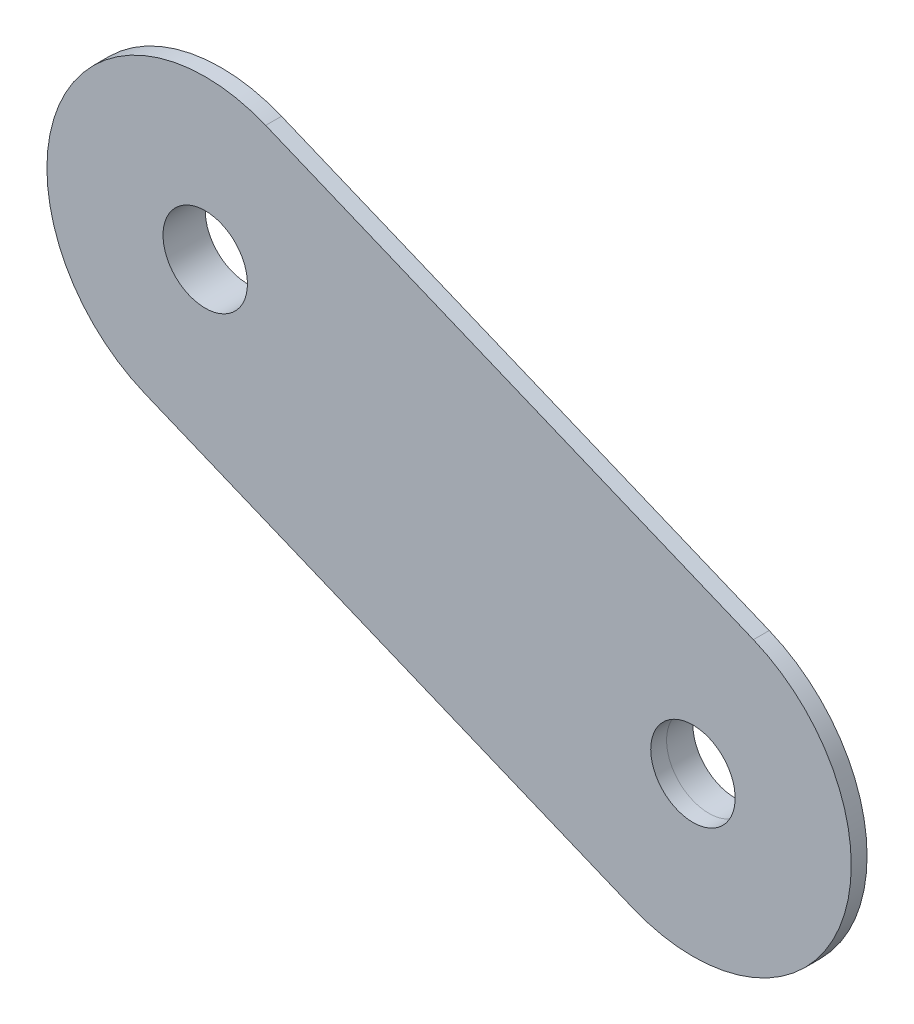
SolidWorks part; units mm, degrees
ref_plane "Front Plane" through (0, 0, 0) normal (0, 0, 1) x (1, 0, 0)
ref_plane "Top Plane" through (0, 0, 0) normal (0, 1, 0) x (1, 0, 0)
ref_plane "Right Plane" through (0, 0, 0) normal (1, 0, 0) x (0, 0, -1)
sketch "Sketch1" plane through (0, 0, 0) normal (0, 0, 1) x (1, 0, 0)
  line L0 (0, 0) -> (46.2112, -19.0925) construction
  line L1 (23.1056, -9.5462) -> (26.6464, -0.9762) construction
  circle A0 centre (0, 0) radius 7.5
  circle A1 centre (0, 0) radius 4
  circle A2 centre (0, 0) radius 4 construction
  circle A3 centre (46.2112, -19.0925) radius 4
  circle A4 centre (46.2112, -19.0925) radius 7.5
  dimension "D1" = 15
extrude "Boss-Extrude1" add sketch "Sketch1" along normal blind 2.5
sketch "Sketch2" plane through (0, 0, 2.5) normal (0, 0, 1) x (1, 0, 0)
  line L0 (0, 0) -> (46.2112, -19.0925) construction
  line L1 (23.1056, -9.5462) -> (26.4754, -1.39) construction
  line L2 (5.7277, 13.8634) -> (51.939, -5.2291)
  line L3 (-5.7277, -13.8634) -> (40.4835, -32.9558)
  arc A0 (5.7277, 13.8634) -> (-5.7277, -13.8634) centre (0, 0) ccw
  circle A1 centre (0, 0) radius 4
  circle A2 centre (0, 0) radius 4 construction
  circle A3 centre (46.2112, -19.0925) radius 4
  arc A4 (51.939, -5.2291) -> (40.4835, -32.9558) centre (46.2112, -19.0925) cw
  dimension "D1" = 30
extrude "Boss-Extrude2" add sketch "Sketch2" along normal blind 1.5
